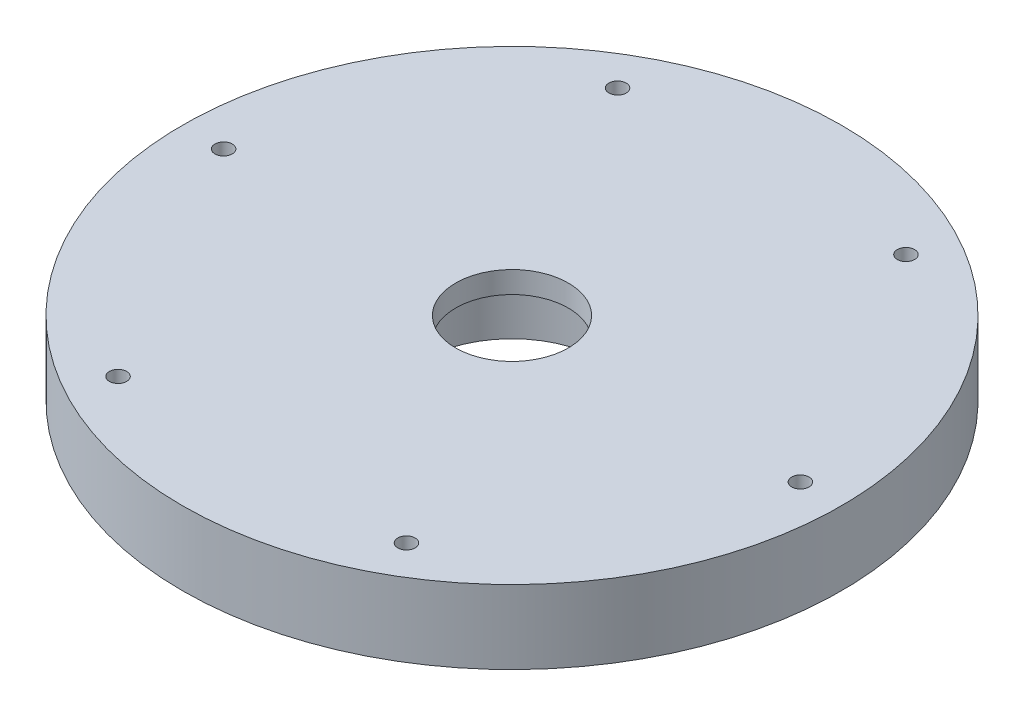
SolidWorks part; units mm, degrees
material "1060 Alloy"
ref_plane "Front Plane" through (0, 0, 0) normal (0, 0, 1) x (1, 0, 0)
ref_plane "Top Plane" through (0, 0, 0) normal (0, 1, 0) x (1, 0, 0)
ref_plane "Right Plane" through (0, 0, 0) normal (1, 0, 0) x (0, 0, -1)
sketch "Sketch1" plane through (0, 0, 0) normal (0, 0, 1) x (1, 0, 0)
  line L0 (0, 38.7087) -> (0, -19.5852) construction
  line L1 (-6.5, 0) -> (-38.0375, 0)
  line L2 (-38.0375, 0) -> (-38.0375, -8.5)
  line L4 (-10.5, -9.75) -> (-10.5, -2.5)
  line L5 (-10.5, -2.5) -> (-6.5, -2.5)
  line L6 (-6.5, -2.5) -> (-6.5, 0)
  line L7 (-10.5, -9.75) -> (-35.0375, -9.75)
  line L8 (-35.0375, -9.75) -> (-35.0375, -8.5)
  line L9 (-35.0375, -8.5) -> (-38.0375, -8.5)
  dimension "D1" = 6.5
  dimension "D2" = 10.5
  dimension "D4" = 38.0375
  dimension "D5" = 3
  dimension "D6" = 1.25
  dimension "D7" = 2.5
  dimension "D3" = 6
revolve "Revolve1" add sketch "Sketch1" angle 360 about L0
sketch "Sketch2" plane through (0, -9.75, 0) normal (0, -1, 0) x (1, 0, 0)
  circle A0 centre (0, 0) radius 33.2875 construction
  circle A1 centre (-33.2875, 0) radius 1
  circle A2 centre (-16.6438, 28.8278) radius 1
  circle A3 centre (16.6437, 28.8278) radius 1
  circle A4 centre (33.2875, 0) radius 1
  circle A5 centre (16.6438, -28.8278) radius 1
  circle A6 centre (-16.6437, -28.8278) radius 1
  point P17 (0, 0)
  dimension "D1" = 2
  dimension "D3" = 66.575
  dimension "D2" = 6
extrude "Cut-Extrude1" cut sketch "Sketch2" against normal through all
equation "\"Stator_OD\"= 60'No Tolerance given"
equation "\"A\"=35.81 'taken off spec sheet for 06808 (A)"
equation "\"Rotor_ID\"= 30'No Tolerance Given"
equation "\"back_bearing_Thickness\"= 5'-0.12"
equation "\"back_bearing_OD\"= 24'-0.009 https://www.mcmaster.com/5972K155/"
equation "\"Stator_Gap\"= 0.0375'+- 0.0125 (From 1.3.3.1 Kollmorgen manual)"
equation "\"Back_mount_hole\"= 1.75'To be tapped to M2 (USE LOCKTITE)"
equation "\"facePlate_Mount_Hole\"= 5.75'To be tapped to M6"
equation "\"back_bearing_ID\"= 15'"
equation "\"final_shaftD\"= 12'To fit in harmonic"
equation "\"final_shaftL\"= 50'random length. Idk"
equation "\"back_bearing_IDOD\"= 16.5'measured off CAD, actually 16.75, but rounded down to nicer number"
equation "\"rotor_shaftD\"= \"Rotor_ID\" - (\"rotor-shaft_gap\")*2'"
equation "\"front_bearing_ID\"= 12'https://www.mcmaster.com/5972K154/"
equation "\"front_bearing_OD\"= 21'-0.009"
equation "\"front_bearing_IDOD\"= 13.5'Measured off CAD. Actually 13.75, but rounded down"
equation "\"front_bearing_Thickness\"= 5'-0.12"
equation "\"rotor_thickness\"= 2.4'measured off CAD"
equation "\"rotor_height\"= 32.86'+-0.075 taken off spec sheet for 06826 (C)"
equation "\"D1@Sketch1\"=\"final_shaftD\"/2+0.5"
equation "\"D2@Sketch1\"=\"front_bearing_OD\"/2"
equation "\"D4@Sketch1\"=\"Stator_OD\"/2+\"Stator_Gap\"+8"
equation "\"D3@Sketch1\"=\"front_bearing_Thickness\"+1"
equation "\"D3@Sketch2\"= \"Stator_OD\" + \"Stator_Gap\" * 2 + 6.5"
equation "\"D1@Sketch2\"=\"Back_mount_hole\"+0.25"
